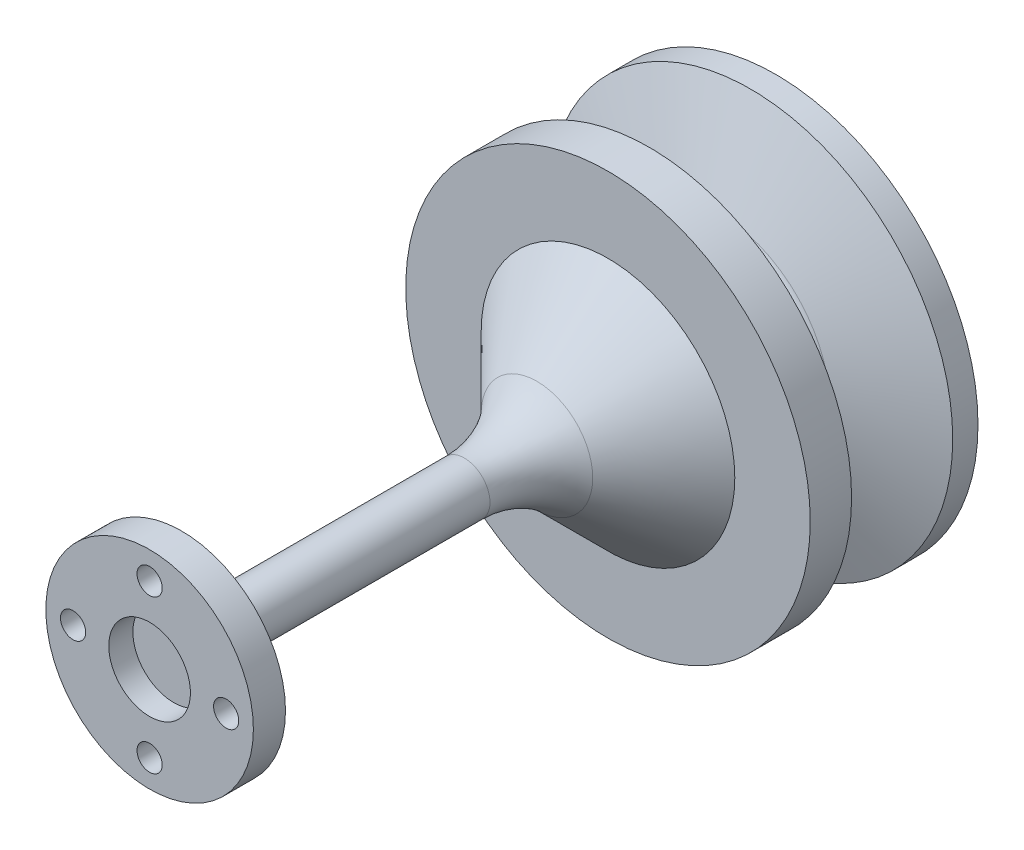
SolidWorks part; units mm, degrees
ref_plane "Plan de face" through (0, 0, 0) normal (0, 0, 1) x (1, 0, 0)
ref_plane "Plan de dessus" through (0, 0, 0) normal (0, 1, 0) x (1, 0, 0)
ref_plane "Plan de droite" through (0, 0, 0) normal (1, 0, 0) x (0, 0, -1)
sketch "Esquisse1" plane through (0, 0, 0) normal (0, 0, 1) x (1, 0, 0)
  circle A0 centre (0, 0) radius 20
  dimension "D1" = 40
extrude "Boss.-Extru.1" add sketch "Esquisse1" along normal mid plane 15
sketch "Esquisse4" plane through (0, 0, 0) normal (1, 0, 0) x (0, 0, -1)
  line L0 (-5, 20) -> (-1.3249, 10)
  line L1 (7.5, 20) -> (-7.5, 20) construction
  line L2 (-1.3249, 10) -> (1.3249, 10)
  line L3 (1.3249, 10) -> (5, 20)
  line L4 (5, 20) -> (-5, 20)
  line L5 (-15.7886, 0) -> (16.0217, 0) construction
  point P4 (0, 20)
  point P7 (0, 10)
  dimension "D1" = 10
  dimension "D2" = 10
  dimension "D3" = 3.6751
revolve "Enlèvement de matière-Révolution1" cut sketch "Esquisse4" angle 360 about L5
fillet "Congé1" radius 1.7 1 edges at (10, 0, -1.3249)
fillet "Congé3" radius 1.7 1 edges at (10, 0, 1.3249)
sketch "Esquisse5" plane through (0, 0, 7.5) normal (0, 0, 1) x (1, 0, 0)
  circle A0 centre (0, 0) radius 5
  dimension "D1" = 10
extrude "Enlèv. mat.-Extru.1" cut sketch "Esquisse5" against normal through all
sketch "Esquisse8" plane through (0, 0, 7.5) normal (0, 0, 1) x (1, 0, 0)
  circle A0 centre (0, 0) radius 2.54
  dimension "D1" = 5.08
extrude "Boss.-Extru.3" add sketch "Esquisse8" along normal blind 43.7388 separate body
sketch "Esquisse9" plane through (0, 0, 7.5) normal (0, 0, 1) x (1, 0, 0)
  circle A0 centre (0, 0) radius 20
extrude "Boss.-Extru.4" add sketch "Esquisse9" along normal blind 1.5875
sketch "Esquisse10" plane through (0, 0, 51.2388) normal (0, 0, 1) x (1, 0, 0)
  circle A0 centre (0, 0) radius 10.2616
  dimension "D1" = 20.5232
extrude "Boss.-Extru.5" add sketch "Esquisse10" along normal blind 3.175
sketch "Esquisse11" plane through (0, 0, 54.4138) normal (0, 0, 1) x (1, 0, 0)
  circle A0 centre (0, 7.5692) radius 1.2446
  dimension "D1" = 2.4892
  dimension "D2" = 7.5692
extrude "Enlèv. mat.-Extru.3" cut sketch "Esquisse11" against normal up to next
pattern_circular "Répétition circulaire2" count 4 over 360 about axis through (0, 0, 54.4138) along (0, 0, 1) of "Enlèv. mat.-Extru.3"
sketch "Esquisse12" plane through (0, 0, 54.4138) normal (0, 0, 1) x (1, 0, 0)
  circle A0 centre (0, 0) radius 4.0386
  dimension "D1" = 8.0772
extrude "Enlèv. mat.-Extru.4" cut sketch "Esquisse12" against normal blind 2.3813
chamfer "Chamfer1" distance 10 angle 45 1 edges at (2.54, 0, 9.0875)
fillet "Fillet1" radius 10.16 1 edges at (2.54, 0, 19.0875)
